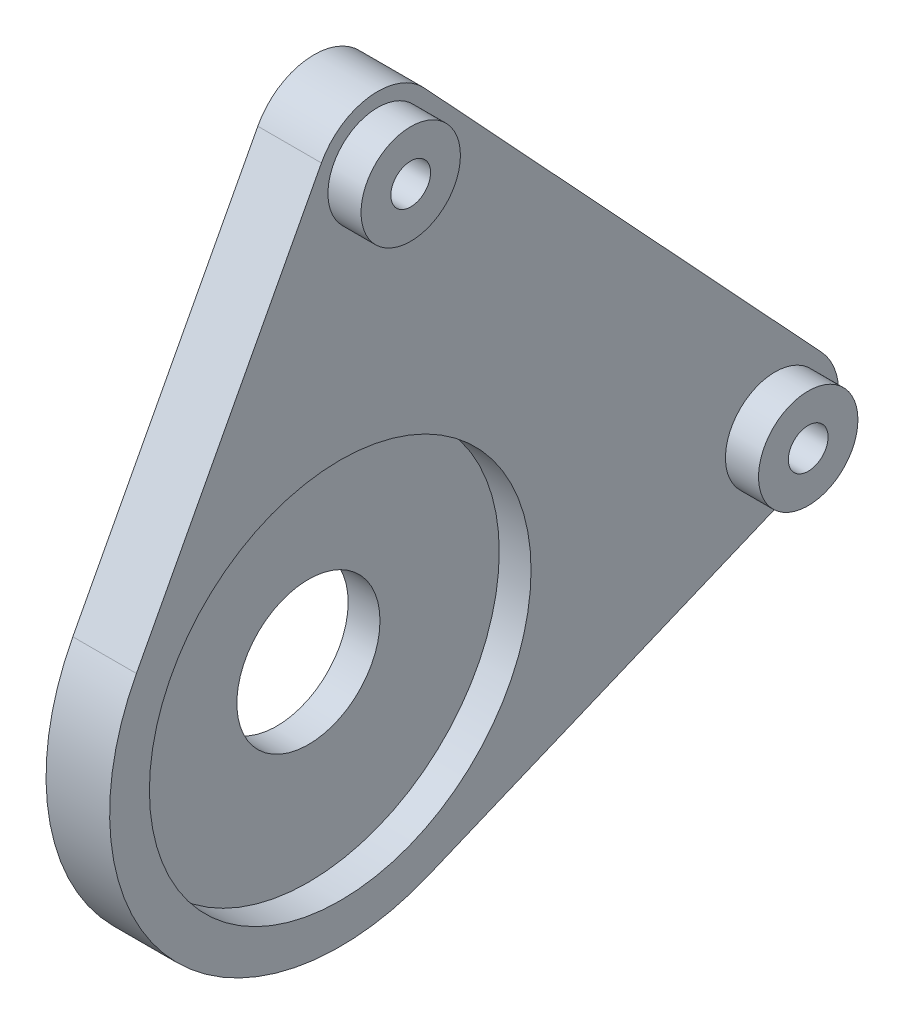
SolidWorks part; units mm, degrees
ref_plane "Front Plane" through (0, 0, 0) normal (0, 0, 1) x (1, 0, 0)
ref_plane "Top Plane" through (0, 0, 0) normal (0, 1, 0) x (1, 0, 0)
ref_plane "Right Plane" through (0, 0, 0) normal (1, 0, 0) x (0, 0, -1)
sketch "Sketch1" plane through (0, 0, 0) normal (1, 0, 0) x (0, 0, -1)
  line L0 (-1.1823, 28.7681) -> (-12.8163, 6.7817)
  line L1 (5.2833, 29.6203) -> (30.28, 2.723)
  line L2 (28.8856, -3.6935) -> (5.5667, -13.3889)
  line L3 (2.3532, 26.8973) -> (0, 0) construction
  line L4 (0, 0) -> (0, 26.8973) construction
  line L5 (0, 26.8973) -> (2.3532, 26.8973) construction
  circle A0 centre (0, 0) radius 4.5
  circle A1 centre (2.3532, 26.8973) radius 1.25
  circle A2 centre (27.35, 0) radius 1.25
  circle A3 centre (0, 0) radius 12
  circle A4 centre (27.35, 0) radius 4
  circle A5 centre (2.3532, 26.8973) radius 4
  circle A6 centre (0, 0) radius 14.5
  circle A7 centre (2.3532, 26.8973) radius 3.125
  circle A8 centre (27.35, 0) radius 3.125
  point P19 (3.4319, 24.1069)
  dimension "D1" = 2.5
  dimension "D2" = 9
  dimension "D3" = 24
  dimension "D6" = 8
  dimension "D7" = 8
  dimension "D8" = 29
  dimension "D9" = 6.25
  dimension "D4" = 27
  dimension "D5" = 27.35
  dimension "D10" = 5
extrude "Boss-Extrude1" add sketch "Sketch1" along normal blind 4 contours A6 A3 | A6 L2 A4 L1 A5 L0 | A5 A1 | A4 A2 | A7 A1 | A8 A2 region at (0, 10.3327, -11.5599) region at (0, 30.7508, -1.8453) region at (0, 13.6748, -3.395) region at (0, 1.4215, -30.9676) region at (0, 26.8973, 0.6834) region at (0, 0, -24.3134)
extrude "Boss-Extrude2" add sketch "Sketch1<3>" along normal blind 6.08 contours A7 A1 | A8 A2 region at (0, 26.8973, 0.6834) region at (0, 0, -24.3134)
sketch "Sketch1<3>" plane through (0, 0, 0) normal (1, 0, 0) x (0, 0, -1) same geometry as "Sketch1"
extrude "Boss-Extrude3" add sketch "Sketch1<4>" along normal blind 2 contours A3 A0 region at (0, 0, 11.6606)
sketch "Sketch1<4>" plane through (0, 0, 0) normal (1, 0, 0) x (0, 0, -1) same geometry as "Sketch1"
equation "\"D5@Sketch1\"=21.60mm+2.5/2+9/2"
